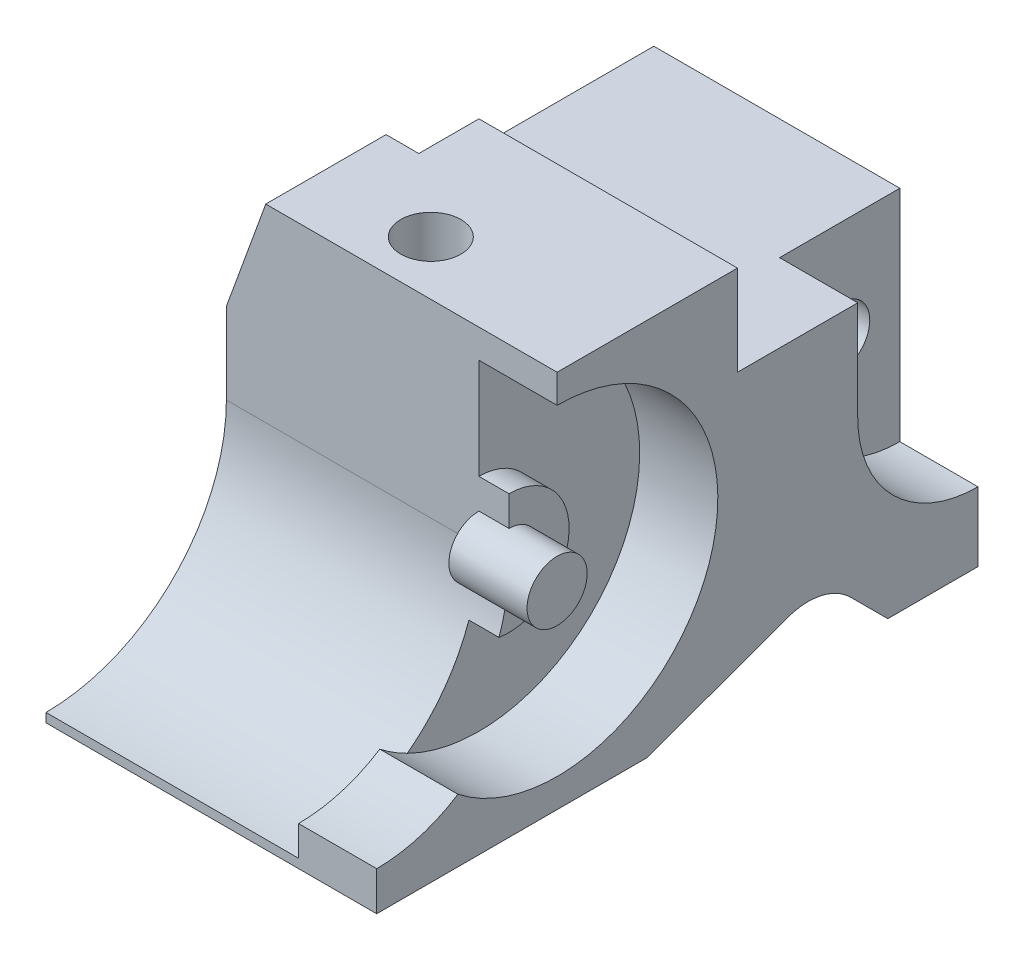
SolidWorks part; units mm, degrees
material "Copper"
ref_plane "Front Plane" through (0, 0, 0) normal (0, 0, 1) x (1, 0, 0)
ref_plane "Top Plane" through (0, 0, 0) normal (0, 1, 0) x (1, 0, 0)
ref_plane "Right Plane" through (0, 0, 0) normal (1, 0, 0) x (0, 0, -1)
sketch "Sketch2" plane through (0, 0, 0) normal (1, 0, 0) x (0, 0, -1)
  line L0 (0, 0) -> (0, 31.5)
  line L1 (0, 31.5) -> (30, 31.5)
  line L2 (30, 31.5) -> (30, 16.5)
  line L3 (30, 16.5) -> (50, 16.5)
  line L4 (50, 16.5) -> (60, 16.5)
  line L5 (60, 16.5) -> (70, 16.5)
  line L6 (70, 16.5) -> (70, -31.5)
  line L7 (70, -31.5) -> (55, -31.5)
  line L8 (-30, -31.5) -> (-30, -21.5)
  line L9 (15, -31.5) -> (38.3397, -23.0051)
  line L10 (48.8309, -25.3309) -> (55, -31.5)
  line L11 (50, 16.5) -> (50, -20)
  line L12 (50, -20) -> (70, -20)
  line L13 (15, -31.5) -> (-30, -31.5)
  circle A0 centre (0, 0) radius 5
  arc A4 (38.3397, -23.0051) -> (48.8309, -25.3309) centre (41.7599, -32.402) cw
  circle A5 centre (60, 0) radius 5
  arc A7 (-7.2569, -6.8803) -> (0, 10) centre (0, 0) ccw
  arc A8 (-30, -21.5) -> (-5.1788, 0.515) centre (-30, 3.5) ccw
  arc A9 (-18.9043, -18.9028) -> (0, 26.7336) centre (0, 0) ccw
  arc A10 (-4.9998, -0.039) -> (-5.2523, -0.043) centre (0, -320.4779) ccw
  arc A11 (0, 0) -> (-30, -30) centre (-30, 0) cw
  point P16 (55, -31.5)
  point P17 (15, -31.5)
  point P24 (70, 16.5)
  point P35 (-77.0155, 4.2412)
  point P36 (0, 0)
  dimension "D2" = 25
  dimension "D3" = 10
  dimension "D4" = 10
  dimension "D7" = 100
  dimension "D10" = 20
  dimension "D11" = 26.7336
  dimension "D12" = 320.4779
  dimension "D5" = 20
  dimension "D6" = 45
  dimension "D8" = 15
  dimension "D9" = 63
  dimension "D13" = 5.1788
extrude "Boss-Extrude4" add sketch "Sketch2" along normal blind 13 contours A9 A11 L8 L13 L9 A4 L10 L7 L6 L12 L11 L3 L2 L1 L0 | L0 A11 A0 | A11 L0 A0 | A11 A9 A8 L8 region at (0, -5.8855, -31.0585) region at (0, -0.0652, -2.083) region at (0, 0.0675, 2.158) region at (0, -24.6867, 22.5042)
extrude "Boss-Extrude5" add sketch "Sketch2<6>" along normal blind 5 contours A0 A11 A7 L0 region at (0, -0.8169, -9.7342)
sketch "Sketch2<6>" plane through (0, 0, 0) normal (1, 0, 0) x (0, 0, -1) same geometry as "Sketch2"
fillet "Fillet2" radius 20 1 edges at (6.5, -20, -50)
extrude "Boss-Extrude6" add sketch "Sketch2<7>" against normal blind 42 contours L11 L12 L6 L5 L4 A5 | A9 A11 L8 L13 L9 A4 L10 L7 L6 L12 L11 L3 L2 L1 L0 | A7 A11 A9 L0 | A0 A11 A7 L0 | L0 A11 A0 region at (0, -0.8169, -9.7342) region at (0, -1.953, -10.9321) region at (0, -5.8855, -31.0585) region at (0, -0.0652, -2.083) region at (0, 16.0838, -55)
sketch "Sketch2<7>" plane through (0, 0, 0) normal (1, 0, 0) x (0, 0, -1) same geometry as "Sketch2"
sketch "Sketch5" plane through (13, 0, 0) normal (1, 0, 0) x (0, 0, -1)
  circle A0 centre (-30, 0) radius 25
  point P0 (-30, 0)
  dimension "D1" = 50
extrude "Cut-Extrude1" cut sketch "Sketch5" against normal blind 42
sketch "Sketch7" plane through (0, 31.5, 0) normal (0, 1, 0) x (1, 0, 0)
  line L0 (-42, 30) -> (-42, 20)
  line L1 (-42, 20) -> (-30, 20)
  line L2 (-30, 20) -> (-30, 30)
  line L3 (-30, 30) -> (-42, 30)
extrude "Cut-Extrude2" cut sketch "Sketch7" against normal blind 239
sketch "Sketch8" plane through (0, 31.5, 0) normal (0, 1, 0) x (1, 0, 0)
  line L0 (13, 0) -> (-17, 0)
  line L1 (13, -5) -> (13, 5) construction
  line L2 (-42, 0) -> (0, 0) construction
  line L3 (-17, 0) -> (-17, 9)
  circle A0 centre (-17, 9) radius 5
extrude "Cut-Extrude3" cut sketch "Sketch8" against normal blind 130 contours A0 region at (-13.5645, 31.5, -5.5645)
sketch "Sketch9" plane through (0, 0, 0) normal (0, 0, 1) x (1, 0, 0)
  line L0 (-42, 31.5) -> (-42, 13.5)
  line L1 (-42, 0) -> (-42, 31.5) construction
  line L2 (-42, 13.5) -> (-35.4485, 31.5)
  line L3 (-35.4485, 31.5) -> (-42, 31.5)
  dimension "D1" = 20
extrude "Cut-Extrude4" cut sketch "Sketch9" against normal blind 130
sketch "Sketch10" plane through (-42, 0, 0) normal (-1, 0, 0) x (0, 0, 1)
  line L0 (-20, 13.5) -> (0, 13.5) construction
  line L1 (-15, -31.5) -> (-0.6671, -31.5)
  line L2 (-15, -31.5) -> (-15, 13.5)
  line L3 (-15, 13.5) -> (-0.6671, 13.5)
  line L4 (-0.6671, -31.5) -> (-0.6671, 13.5)
  line L6 (-24.5466, -31.5) -> (-15, -31.5)
  line L7 (-24.5466, -31.5) -> (-24.5466, 13.5)
  line L8 (-24.5466, 13.5) -> (-15, 13.5)
  line L9 (-15, -31.5) -> (-15, 13.5)
  line M2 (0, 13.5) -> (-20, 13.5)
  line M3 (-20, 13.5) -> (-20, -29.6801)
  line M4 (-20, -29.6801) -> (-15, -31.5)
extrude "Cut-Extrude6" cut sketch "Sketch10" against normal blind 37 contours L2 M4 M2 M3 | L3 L4 L1 L2 region at (-42, -8.5482, -17.4828)
